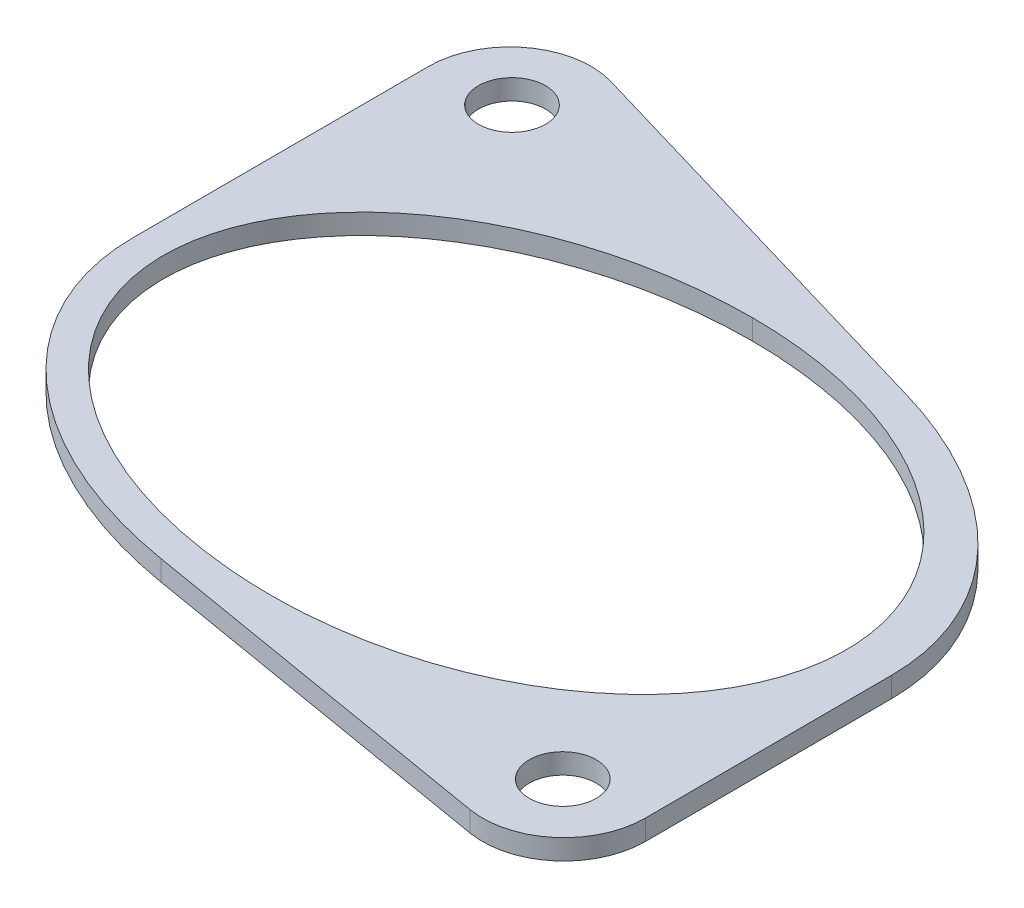
SolidWorks part; units mm, degrees
material "ABS"
ref_plane "Front Plane" through (0, 0, 0) normal (0, 0, 1) x (1, 0, 0)
ref_plane "Top Plane" through (0, 0, 0) normal (0, 1, 0) x (1, 0, 0)
ref_plane "Right Plane" through (0, 0, 0) normal (1, 0, 0) x (0, 0, -1)
sketch "Sketch1" plane through (0, 0, 0) normal (0, 1, 0) x (1, 0, 0)
  line L0 (-18.17, 0) -> (-18.67, 0) construction
  line L1 (0, 13.35) -> (0, 12.85) construction
  line L2 (-18.17, 0) -> (-17.17, 0) construction
  line L3 (0, 12.85) -> (0, 11.85) construction
  line L4 (-18.7099, 19.9501) -> (-18.67, -0.0191)
  line L5 (-18.7099, 19.9501) -> (7.1116, 12.3436)
  line L6 (-15, 15) -> (-13.9545, 18.5492) construction
  line L7 (-15, 15) -> (-18.7, 14.9926) construction
  line L8 (18.67, 0.0229) -> (18.7105, -16.8795)
  line L9 (18.7105, -16.8795) -> (-4.2939, -12.9921)
  line L10 (15, -12.5) -> (18.7, -12.4911) construction
  line L11 (15, -12.5) -> (14.3835, -16.1483) construction
  circle A0 centre (15, -12.5) radius 1.65
  circle A1 centre (-15, 15) radius 1.65
  ellipse E0 centre (0, 0) end of major axis (-18.17, 0) minor radius 12.85 construction
  ellipse E1 centre (0, 0) end of major axis (-17.17, 0) minor radius 11.85 (0, 11.85) -> (0, -11.85) ccw
  ellipse E2 centre (0, 0) end of major axis (18.67, 0) minor radius 13.35 (-18.67, 0) -> (-4.2939, -12.9921) ccw
  ellipse E3 centre (0, 0) end of major axis (16.47, 0) minor radius 11.85 (0, 11.85) -> (0, -11.85) cw
  ellipse E4 centre (0, 0) end of major axis (18.67, 0) minor radius 13.35 (18.67, 0.0229) -> (0, 13.35) ccw
  dimension "D10" = 3.3
  dimension "D1" = 12.85
  dimension "D2" = 18.17
  dimension "D3" = 15
  dimension "D4" = 1
  dimension "D5" = 0.5
  dimension "D6" = 15
  dimension "D7" = 1.7
  dimension "D8" = 15
  dimension "D9" = 12.5
  dimension "D11" = 3.7
extrude "Boss-Extrude1" add sketch "Sketch1" along normal blind 1 contours L8 E4 L5 L4 E2 L9 E1 E3 A0 A1 region at (-5.9475, 0, -15.6432)
fillet "Fillet1" radius 4 2 edges at (18.7105, 0.5, 16.8795) (-18.7099, 0.5, -19.9501)
